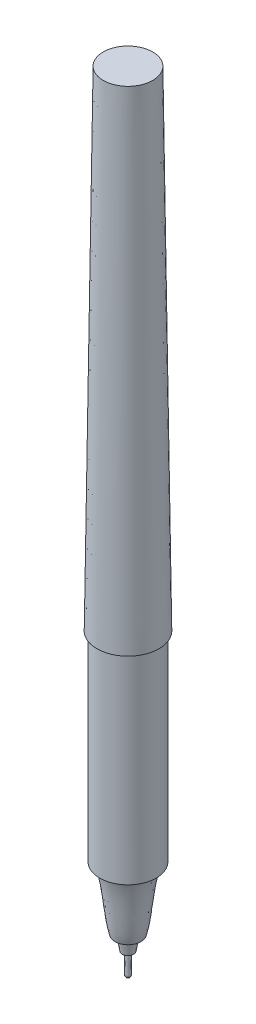
SolidWorks part; units mm, degrees
ref_plane "Front Plane" through (0, 0, 0) normal (0, 0, 1) x (1, 0, 0)
ref_plane "Top Plane" through (0, 0, 0) normal (0, 1, 0) x (1, 0, 0)
ref_plane "Right Plane" through (0, 0, 0) normal (1, 0, 0) x (0, 0, -1)
sketch "Sketch1" plane through (0, 0, 0) normal (0, 1, 0) x (1, 0, 0)
  circle A0 centre (0, 0) radius 4.9911
  dimension "D1" = 9.9822
sketch3d "3DSketch1" plane through (0, 0, 0) normal (0, 0, 1) x (1, 0, 0)
  dimension "D1" = 78.74
sketch "Sketch8" plane through (0, 0, 0) normal (1, 0, 0) x (0, 0, -1)
  line L0 (0, -1000) -> (0, 49000) construction
sketch "Sketch9" plane through (0, 78.74, 0) normal (0, 1, 0) x (-1, 0, 0)
  circle A0 centre (0, 0) radius 3.9782
  dimension "D1" = 7.9565
loft "Loft2" add profiles "Sketch1", "Sketch9" connector at (3.5403, 0, -3.5181) connector at (2.4978, 78.74, -3.0964)
sketch "Sketch11" plane through (0, 0, 0) normal (0, -1, 0) x (1, 0, 0)
  circle A0 centre (0, 0) radius 4.5466
  dimension "D1" = 9.0932
extrude "Boss-Extrude6" add sketch "Sketch11" along normal blind 32.1945
sketch "Sketch12" plane through (0, 0, 0) normal (0, 0, 1) x (1, 0, 0)
  line L0 (0, -201000) -> (0, 249000) construction
  line L1 (0, -32.1945) -> (3.8608, -32.1945)
  line L2 (-4.5466, -32.1945) -> (4.5466, -32.1945) construction
  line L3 (0, -42.2783) -> (2.1019, -42.2783)
  line L4 (0, -32.1945) -> (0, -42.2783)
  spline S0 degree 3 poles (3.8608, -32.1945) (2.8705, -34.9719) (2.8125, -39.8412) (2.1018, -42.2783) knots 0 0 0 0 1 1 1 1
  dimension "D3" = 10.0838
  dimension "D1" = 3.8608
  dimension "D2" = 2.1019
revolve "Revolve1" add sketch "Sketch12" angle 360 about L0
sketch "Sketch13" plane through (0, 0, 0) normal (0, 0, 1) x (1, 0, 0)
  line L0 (0, -42.2783) -> (1.3144, -42.2783)
  line L1 (-2.1018, -42.2783) -> (2.1018, -42.2783) construction
  line L2 (1.3144, -42.2783) -> (0.9207, -44.6278)
  line L3 (0.9207, -44.6278) -> (0, -44.6278)
  line L4 (0, -201000) -> (0, 249000) construction
  line L5 (0, -42.2783) -> (0, -44.6278)
  dimension "D1" = 1.3144
  dimension "D2" = 0.9207
  dimension "D3" = 2.3495
revolve "Revolve2" add sketch "Sketch13" angle 360 about L0
sketch "Sketch14" plane through (0, 0, 0) normal (0, 0, 1) x (1, 0, 0)
  line L0 (0, -44.6278) -> (0.4001, -44.6278)
  line L1 (0, -201000) -> (0, 249000) construction
  line L2 (0.4001, -44.6278) -> (0.4001, -47.9044)
  line L3 (-0.9207, -44.6278) -> (0.9207, -44.6278) construction
  line L4 (0, -44.6278) -> (0, -48.3108)
  arc A0 (0.4001, -47.9044) -> (0, -48.3108) centre (-0.0063, -47.9044) cw
  dimension "D2" = 0.4064
  dimension "D1" = 0.4001
  dimension "D3" = 3.683
revolve "Revolve3" add sketch "Sketch14" angle 360 about L0
